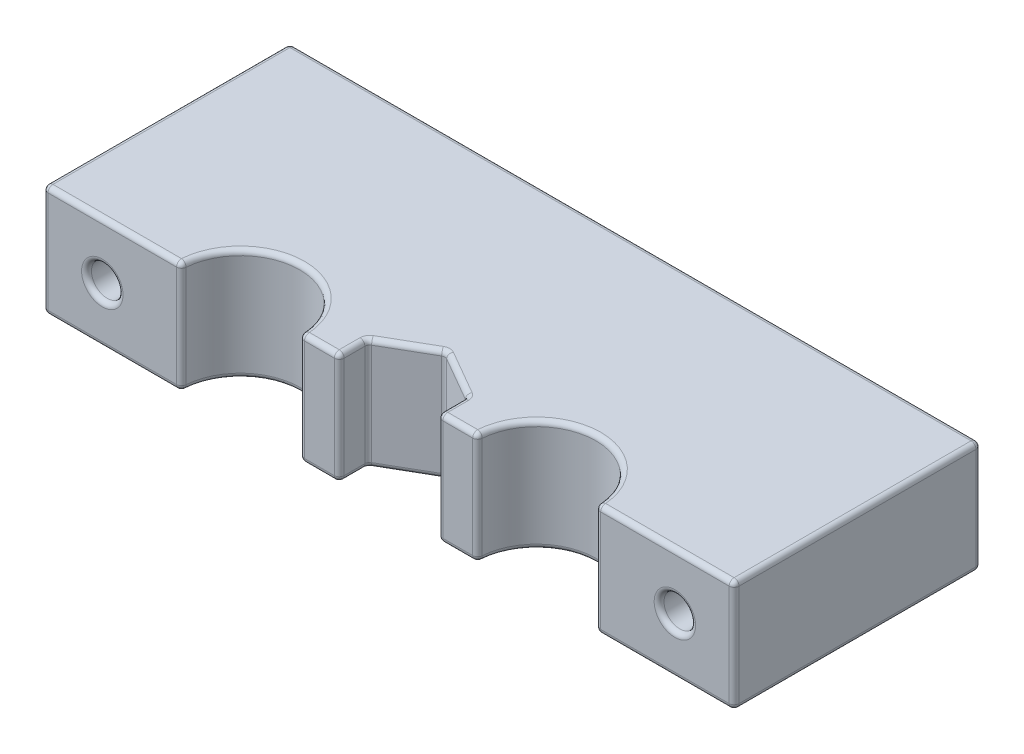
SolidWorks part; units mm, degrees
ref_plane "Front Plane" through (0, 0, 0) normal (0, 0, 1) x (1, 0, 0)
ref_plane "Top Plane" through (0, 0, 0) normal (0, 1, 0) x (1, 0, 0)
ref_plane "Right Plane" through (0, 0, 0) normal (1, 0, 0) x (0, 0, -1)
sketch "Sketch1" plane through (0, 0, 0) normal (0, 1, 0) x (1, 0, 0)
  line L0 (35, 0) -> (35, 25) construction
  line L5 (0, 0) -> (70, 0) construction
  line L6 (0, 0) -> (0, 25) construction
  line L13 (0, 25) -> (70, 25) construction
  line L14 (70, 0) -> (70, 25) construction
  line L15 (56, 0) -> (70, 0)
  line L16 (30, 2.8868) -> (30, -2.8868) construction
  line L17 (30, -2.8868) -> (35, -5.7735) construction
  line L18 (35, -5.7735) -> (40, -2.8868) construction
  line L19 (40, -2.8868) -> (40, 2.8868) construction
  line L20 (40, 2.8868) -> (35, 5.7735) construction
  line L21 (35, 5.7735) -> (30, 2.8868) construction
  line L22 (70, 0) -> (70, 25)
  line L23 (70, 25) -> (0, 25)
  line L24 (0, 25) -> (0, 0)
  line L25 (0, 0) -> (14, 0)
  line L26 (26, 0) -> (30, 0)
  line L27 (30, 0) -> (30, 2.8868)
  line L28 (30, 2.8868) -> (35, 5.7735)
  line L29 (35, 5.7735) -> (40, 2.8868)
  line L30 (40, 2.8868) -> (40, 0)
  line L31 (40, 0) -> (44, 0)
  circle A2 centre (20, 0) radius 6 construction
  circle A3 centre (35, 0) radius 5 construction
  circle A4 centre (50, 0) radius 6 construction
  arc A5 (14, 0) -> (26, 0) centre (20, 0) cw
  arc A6 (44, 0) -> (56, 0) centre (50, 0) cw
  point P7 (35, 0)
  dimension "D3" = 12
  dimension "D4" = 25
  dimension "D1" = 15
  dimension "D2" = 70
  dimension "D5" = 10
extrude "Boss-Extrude1" add sketch "Sketch1" along normal blind 11.3
sketch "Sketch2" plane through (0, 0, -25) normal (0, 0, -1) x (-1, 0, 0)
  line L0 (-35, 11.3) -> (-35, 0) construction
  line L1 (-70, 11.3) -> (0, 11.3) construction
  line L2 (-70, 0) -> (0, 0) construction
  line L3 (0, 5.65) -> (-6, 5.65) construction
  line L4 (0, 11.3) -> (0, 0) construction
  circle A0 centre (-6, 5.65) radius 1.6
  circle A1 centre (-64, 5.65) radius 1.6
  dimension "D1" = 3.2
  dimension "D2" = 6
extrude "Cut-Extrude1" cut sketch "Sketch2" against normal through all
fillet "Fillet1" radius 0.5 43 edges at (30, 5.65, 0) (30, 5.65, -2.8868) (35, 5.65, -5.7735) (40, 5.65, -2.8868) (65.6, 5.65, 0) (4.4, 5.65, 0) (14, 5.65, 0) (26, 5.65, 0) (44, 5.65, 0) (56, 5.65, 0) (70, 5.65, 0) (0, 5.65, 0) (70, 5.65, -25) (0, 5.65, -25) (65.6, 5.65, -25) (4.4, 5.65, -25) (20, 0, -6) (28, 0, 0) (30, 0, -1.4434) (32.5, 0, -4.3301) (37.5, 0, -4.3301) (40, 0, -1.4434) (42, 0, 0) (50, 0, -6) (63, 0, 0) (70, 0, -12.5) (35, 0, -25) (0, 0, -12.5) (7, 0, 0) (0, 11.3, -12.5) (35, 11.3, -25) (70, 11.3, -12.5) (63, 11.3, 0) (50, 11.3, -6) (42, 11.3, 0) (40, 11.3, -1.4434) (37.5, 11.3, -4.3301) (32.5, 11.3, -4.3301) (30, 11.3, -1.4434) (28, 11.3, 0) (20, 11.3, -6) (7, 11.3, 0) (40, 5.65, 0)
